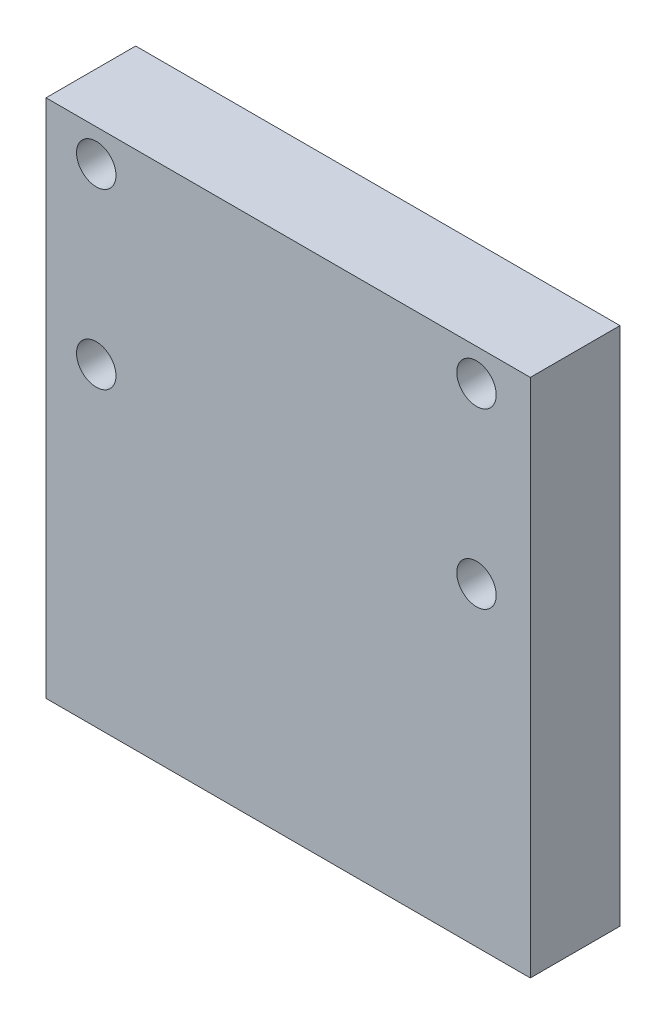
SolidWorks part; units mm, degrees
ref_plane "Front Plane" through (0, 0, 0) normal (0, 0, 1) x (1, 0, 0)
ref_plane "Top Plane" through (0, 0, 0) normal (0, 1, 0) x (1, 0, 0)
ref_plane "Right Plane" through (0, 0, 0) normal (1, 0, 0) x (0, 0, -1)
sketch "Sketch1" plane through (0, 0, 0) normal (0, 0, 1) x (1, 0, 0)
  line L1 (-13.5, 14.5) -> (13.5, 14.5)
  line L2 (-13.5, 14.5) -> (-13.5, -14.5)
  line L3 (-13.5, -14.5) -> (13.5, -14.5)
  line L4 (13.5, 14.5) -> (13.5, -14.5)
  line L5 (-13.5, 14.5) -> (13.5, -14.5) construction
  line L6 (-13.5, -14.5) -> (13.5, 14.5) construction
  point P0 (0, 0)
  dimension "D1" = 27
  dimension "D2" = 29
extrude "Boss-Extrude1" add sketch "Sketch1" along normal blind 5
sketch "Sketch2" plane through (0, -14.5, 0) normal (0, -1, 0) x (1, 0, 0)
  line L0 (-13.5, 2.5) -> (13.5, 2.5) construction
  line L1 (-13.5, 5) -> (-13.5, 0) construction
  line L2 (13.5, 5) -> (13.5, 0) construction
  circle A0 centre (-7, 2.5) radius 1.25
  circle A1 centre (0, 2.5) radius 1.25
  circle A2 centre (7, 2.5) radius 1.25
  point P13 (13.5, 2.5)
  dimension "D1" = 2.5
  dimension "D2" = 7
  dimension "D3" = 7
extrude "Cut-Extrude1" cut sketch "Sketch2" against normal blind 5
sketch "Sketch3" plane through (0, 0, 5) normal (0, 0, 1) x (1, 0, 0)
  line L0 (0, 14.5) -> (0, -14.5) construction
  line L1 (13.5, 14.5) -> (-13.5, 14.5) construction
  line L2 (-13.5, -14.5) -> (13.5, -14.5) construction
  line L3 (-13.5, 0) -> (13.5, 0) construction
  line L4 (-13.5, 14.5) -> (-13.5, -14.5) construction
  line L5 (13.5, -14.5) -> (13.5, 14.5) construction
  line L6 (-12.5, 15.7476) -> (12.5, 15.7476) construction
  line L7 (-13.5, -9.36) -> (13.5, -9.36) construction
  line L8 (-5.4, 5.4) -> (5.4, 5.4) construction
  line L9 (-5.4, 5.4) -> (-5.4, -5.4) construction
  line L10 (-5.4, -5.4) -> (5.4, -5.4) construction
  line L11 (5.4, 5.4) -> (5.4, -5.4) construction
  line L12 (-5.4, 5.4) -> (5.4, -5.4) construction
  line L13 (-5.4, -5.4) -> (5.4, 5.4) construction
  line L14 (-10.7, 5.4) -> (-10.7, 0.65) construction
  circle A0 centre (-10.7, 12.7) radius 1.1
  circle A1 centre (10.5, 12.7) radius 1.1
  circle A2 centre (-10.7, 12.7) radius 2.375 construction
  circle A3 centre (-10.7, 3.025) radius 2.375 construction
  circle A4 centre (-10.7, 3.025) radius 1.1
  circle A5 centre (10.5, 3.025) radius 1.1
  circle A6 centre (0, 0) radius 3.475 construction
  point P22 (0, 15.7476)
  point P24 (0, 0)
  dimension "D1" = 2.2
  dimension "D5" = 4.75
  dimension "D6" = 4.75
  dimension "D8" = 2.2
  dimension "D13" = 6.95
  dimension "D7" = 7.3
  dimension "D2" = 1.8
  dimension "D3" = 1.8
  dimension "D4" = 2
  dimension "D9" = 10.8
  dimension "D10" = 25
  dimension "D11" = 10.8
  dimension "D12" = 7.3
  dimension "D14" = 23.86
  dimension "D15" = 14.5
  dimension "D16" = 21.2
  dimension "D17" = 9.675
  dimension "D18" = 9.36
  dimension "D19" = 14.5
extrude "Cut-Extrude2" cut sketch "Sketch3" against normal blind 10
